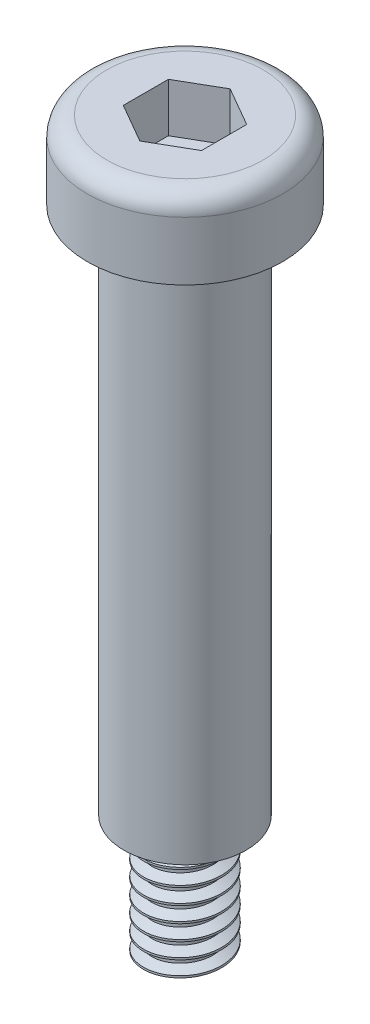
SolidWorks part; units mm, degrees
ref_plane "Front Plane" through (0, 0, 0) normal (0, 0, 1) x (1, 0, 0)
ref_plane "Top Plane" through (0, 0, 0) normal (0, 1, 0) x (1, 0, 0)
ref_plane "Right Plane" through (0, 0, 0) normal (1, 0, 0) x (0, 0, -1)
sketch "Sketch1" plane through (0, 0, 0) normal (0, 0, 1) x (1, 0, 0)
  line L0 (0, 0) -> (0, 7237.937) construction
  line L1 (0, 0) -> (7237.937, 0) construction
  line L2 (-2, 0) -> (-2, 6)
  line L3 (-2, 6) -> (-3.125, 6)
  line L4 (-3.125, 6) -> (-3.125, 33)
  line L5 (-3.125, 33) -> (-5, 33)
  line L6 (-2, 0) -> (0, 0)
  line L7 (0, 37) -> (0, 0)
  line L8 (-5, 33) -> (-5, 37)
  line L9 (-5, 37) -> (0, 37)
  point P12 (0, 0)
  dimension "D1" = 4
  dimension "D2" = 6.25
  dimension "D3" = 6
  dimension "D4" = 27
  dimension "D5" = 10
  dimension "D6" = 4
revolve "Revolve1" add sketch "Sketch1" angle 360 about L0
thread "Thread1" pitch 0.8 method cut trim with start face yes trim with end face yes profile "Thread Profile1" start angle 0, offset 2, length 0, pitch 0.8, diameter 4
ref_plane "Plane1" through (2, -2, 0) normal (0, 0, 1) x (1, 0, 0)
sketch "Thread Profile1" plane through (2, -2, 0) normal (0, 0, 1) x (1, 0, 0)
  line L0 (0, 0) -> (0, 0.8) construction
  line L11 (0, 0) -> (0, 0.7)
  line L12 (0, 0.7) -> (-0.433, 0.45)
  line L13 (-0.433, 0.45) -> (-0.433, 0.25)
  line L15 (-0.433, 0.25) -> (0, 0)
  line L17 (-0.433, 0.35) -> (0, 0.35) construction
  point P2 (0, 0)
  dimension "Pitch" = 0.8
  dimension "Profile_Angle" = 60
  dimension "Profile_Land" = 0.2
  dimension "Profile_Height" = 0.433
fillet "Fillet1" radius 1 1 edges at (0, 37, -5)
sketch "Sketch5" plane through (0, 37, 0) normal (0, 1, 0) x (1, 0, 0)
  line L1 (0, 2.3094) -> (-2, 1.1547)
  line L2 (-2, 1.1547) -> (-2, -1.1547)
  line L3 (-2, -1.1547) -> (0, -2.3094)
  line L4 (0, -2.3094) -> (2, -1.1547)
  line L5 (2, -1.1547) -> (2, 1.1547)
  line L6 (2, 1.1547) -> (0, 2.3094)
  circle A0 centre (0, 0) radius 2 construction
  point P1 (0, 0)
  dimension "D1" = 4
extrude "Cut-Extrude1" cut sketch "Sketch5" against normal blind 2.5
